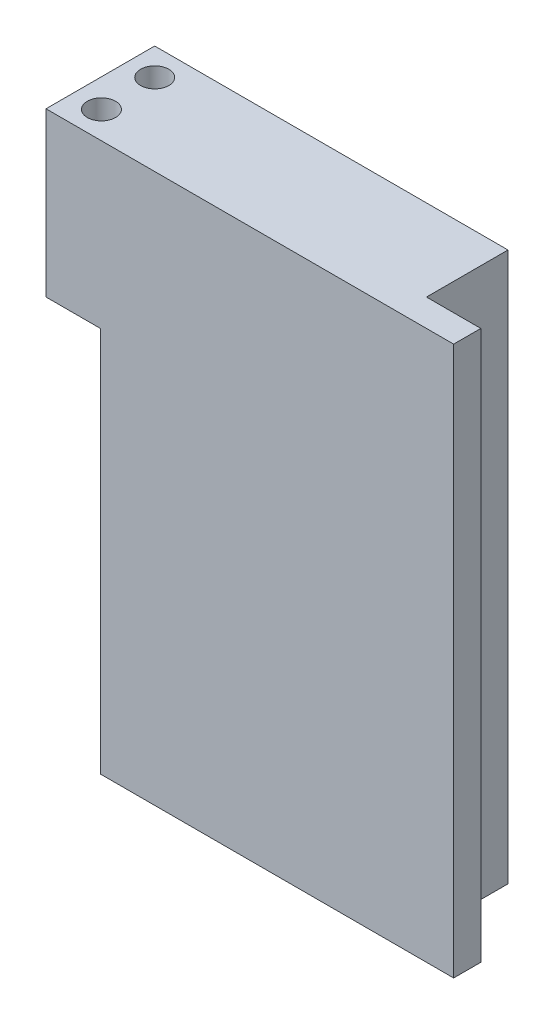
SolidWorks part; units mm, degrees
ref_plane "Front Plane" through (0, 0, 0) normal (0, 0, 1) x (1, 0, 0)
ref_plane "Top Plane" through (0, 0, 0) normal (0, 1, 0) x (1, 0, 0)
ref_plane "Right Plane" through (0, 0, 0) normal (1, 0, 0) x (0, 0, -1)
sketch "Sketch1" plane through (0, 0, 0) normal (0, 1, 0) x (1, 0, 0)
  line L1 (0, 0) -> (82.55, 0)
  line L2 (0, 0) -> (0, -25.4)
  line L3 (0, -25.4) -> (82.55, -25.4)
  line L4 (82.55, 0) -> (82.55, -25.4)
  point P5 (0, 0)
  dimension "D1" = 25.4
  dimension "D2" = 82.55
extrude "Boss-Extrude1" add sketch "Sketch1" along normal blind 127 and the other way blind 1.27 contours L2 L1 L4 L3
sketch "Sketch2" plane through (0, 127, 0) normal (0, 1, 0) x (1, 0, 0)
  line L0 (0, 0) -> (-12.7, 0)
  line L1 (-12.7, 0) -> (-12.7, -25.4)
  line L2 (-12.7, -25.4) -> (0, -25.4)
  line L3 (0, -25.4) -> (0, 0)
  point P3 (91.3749, -23.2561)
  dimension "D1" = 25.4
  dimension "D2" = 12.7
  dimension "D3" = 82.55
extrude "Boss-Extrude2" add sketch "Sketch2" against normal blind 38.1 contours L3 L0 L1 L2
sketch "Sketch3" plane through (0, 127, 0) normal (0, 1, 0) x (1, 0, 0)
  line L2 (-12.7, 0) -> (-12.7, -25.4) construction
  line L3 (-12.7, -25.4) -> (82.55, -25.4) construction
  circle A0 centre (-6.096, -19.05) radius 3.302
  point P0 (0, 0)
  dimension "D2" = 6.604
  dimension "D3" = 6.35
  dimension "D1" = 6.604
extrude "Cut-Extrude1" cut sketch "Sketch3" against normal blind 53.34 contours A0
sketch "Sketch4" plane through (0, 127, 0) normal (0, 1, 0) x (1, 0, 0)
  line L0 (-12.7, 0) -> (82.55, 0) construction
  line L1 (-12.7, 0) -> (-12.7, -25.4) construction
  line L8 (-17.7261, 1.0229) -> (-17.6101, 1.0229)
  circle A0 centre (-6.35, -6.35) radius 3.302
  point P5 (-12.7, -7.6981)
  point P6 (0, 0)
  dimension "D1" = 6.604
  dimension "D2" = 6.35
  dimension "D3" = 6.35
extrude "Cut-Extrude2" cut sketch "Sketch4" against normal blind 72.898 contours A0
sketch "Sketch5" plane through (0, 127, 0) normal (0, 1, 0) x (1, 0, 0)
  line L0 (43.7945, -17.8415) -> (27.3801, -17.8415)
  line L7 (27.3801, -17.8415) -> (61.3304, -21.104)
extrude "Cut-Extrude3" cut sketch "Sketch5" against normal blind 177.8 rebuild error yes
sketch "Sketch6" plane through (0, 127, 0) normal (0, 1, 0) x (1, 0, 0)
  line L0 (82.55, -25.4) -> (80.01, -25.4)
  line L7 (-12.7, -25.4) -> (82.55, -25.4) construction
  line L8 (80.01, -25.4) -> (102.87, -25.4)
extrude "Cut-Extrude4" cut sketch "Sketch6" against normal blind 140.7527 rebuild error yes
sketch "Sketch7" plane through (0, 127, 0) normal (0, 1, 0) x (1, 0, 0)
  line L4 (82.55, -19.05) -> (82.55, 0)
  line L7 (82.55, -19.05) -> (69.85, -19.05)
  line L8 (69.85, -19.05) -> (69.85, 0)
  line L10 (69.85, 0) -> (82.55, 0)
  dimension "D1" = 19.05
  dimension "D2" = 19.05
  dimension "D3" = 12.7
extrude "Cut-Extrude5" cut sketch "Sketch7" against normal through all
